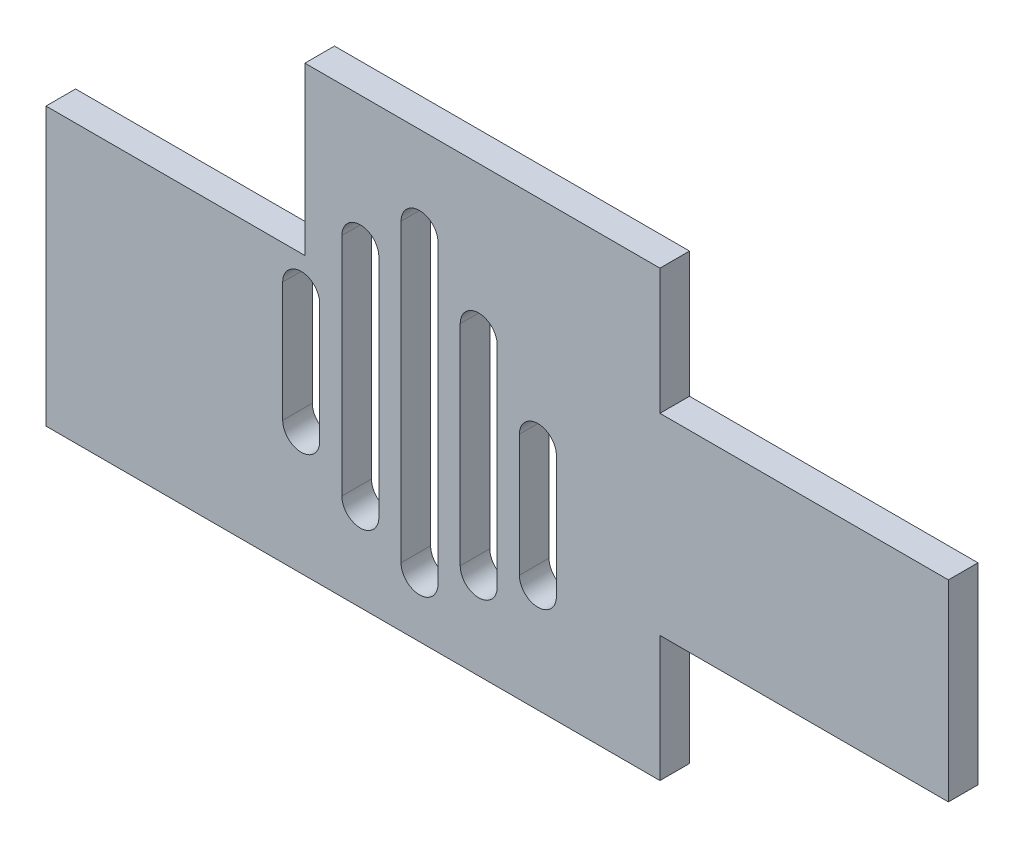
SolidWorks part; units mm, degrees
ref_plane "Front Plane" through (0, 0, 0) normal (0, 0, 1) x (1, 0, 0)
ref_plane "Top Plane" through (0, 0, 0) normal (0, 1, 0) x (1, 0, 0)
ref_plane "Right Plane" through (0, 0, 0) normal (1, 0, 0) x (0, 0, -1)
sketch "Sketch1" plane through (0, 0, 0) normal (0, 0, 1) x (1, 0, 0)
  line L0 (-4.1373, 38.9941) -> (-4.1373, -1.0059)
  line L6 (30.8627, 33.9941) -> (69.8627, 33.9941)
  line L9 (0.8627, 38.9941) -> (0.8627, -1.0059)
  line L12 (-12.1373, 33.3124) -> (-12.1373, 2.8098)
  line L15 (-7.1373, 33.3124) -> (-7.1373, 2.8098)
  line L18 (-15.1373, 23.8613) -> (-15.1373, 7.6834)
  line L21 (30.8627, 7.9941) -> (69.8627, 7.9941)
  line L62 (-17.1373, 50.9941) -> (-17.1373, 28.4723)
  line L63 (-17.1373, 28.4723) -> (-52.1373, 28.4723)
  line L65 (-52.1373, 28.4723) -> (-52.1373, -9.0059)
  line L66 (30.8627, 50.9941) -> (30.8627, 33.9941)
  line L68 (69.8627, 33.9941) -> (69.8627, 7.9941)
  line L70 (30.8627, 7.9941) -> (30.8627, -9.0059)
  line L71 (30.8627, 50.9941) -> (-17.1373, 50.9941)
  line L72 (30.8627, -9.0059) -> (-52.1373, -9.0059)
  line L75 (-20.1373, 23.8613) -> (-20.1373, 7.6834)
  line L77 (3.8627, 30.9941) -> (3.8627, 2.6474)
  line L79 (8.8627, 30.9941) -> (8.8627, 2.6474)
  line L80 (11.8627, 22.0483) -> (11.8627, 5.5385)
  line L81 (16.8627, 22.0483) -> (16.8627, 5.5385)
  circle A13 centre (-1.6373, 38.9941) radius 2.5 construction
  circle A14 centre (-1.6373, -1.0059) radius 2.5 construction
  arc A15 (-4.1373, 38.9941) -> (0.8627, 38.9941) centre (-1.6373, 38.9941) cw
  arc A16 (0.8627, -1.0059) -> (-4.1373, -1.0059) centre (-1.6373, -1.0059) cw
  circle A17 centre (6.3627, 30.9941) radius 2.5 construction
  circle A18 centre (6.3627, 2.6474) radius 2.5 construction
  circle A19 centre (-9.6373, 33.3124) radius 2.5 construction
  circle A20 centre (-9.6373, 2.8098) radius 2.5 construction
  circle A21 centre (-17.6373, 23.8613) radius 2.5 construction
  circle A22 centre (-17.6373, 7.6834) radius 2.5 construction
  circle A23 centre (14.3627, 22.0483) radius 2.5 construction
  circle A24 centre (14.3627, 5.5385) radius 2.5 construction
  arc A27 (-12.1373, 33.3124) -> (-7.1373, 33.3124) centre (-9.6373, 33.3124) cw
  arc A28 (-15.1373, 23.8613) -> (-20.1373, 23.8613) centre (-17.6373, 23.8613) ccw
  arc A29 (-20.1373, 7.6834) -> (-15.1373, 7.6834) centre (-17.6373, 7.6834) ccw
  arc A30 (-12.1373, 2.8098) -> (-7.1373, 2.8098) centre (-9.6373, 2.8098) ccw
  arc A31 (3.8627, 2.6474) -> (8.8627, 2.6474) centre (6.3627, 2.6474) ccw
  arc A32 (11.8627, 5.5385) -> (16.8627, 5.5385) centre (14.3627, 5.5385) ccw
  arc A33 (16.8627, 22.0483) -> (11.8627, 22.0483) centre (14.3627, 22.0483) ccw
  arc A34 (8.8627, 30.9941) -> (3.8627, 30.9941) centre (6.3627, 30.9941) ccw
  point P0 (0, 0)
  dimension "D3" = 5
  dimension "D4" = 3
  dimension "D5" = 3
  dimension "D6" = 3
  dimension "D7" = 3
  dimension "D9" = 12
  dimension "D8" = 26
  dimension "D10" = 13
  dimension "D11" = 60
  dimension "D12" = 8
  dimension "D14" = 35
  dimension "D15" = 39
  dimension "D16" = 48
  dimension "D23" = 40
extrude "Boss-Extrude1" add sketch "Sketch1" along normal blind 4
equation "\"m\"= 3mm"
